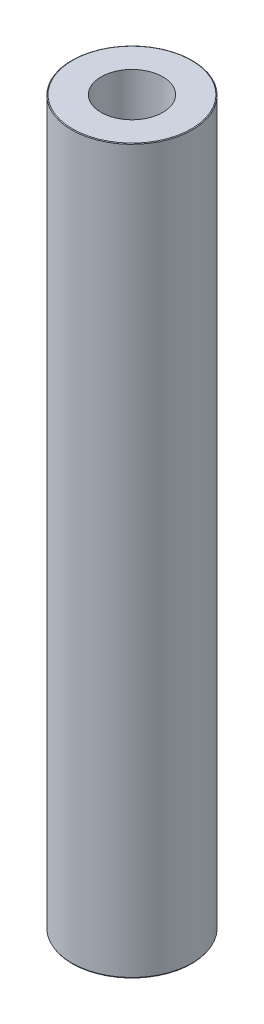
SolidWorks part; units mm, degrees
ref_plane "Front Plane" through (0, 0, 0) normal (0, 0, 1) x (1, 0, 0)
ref_plane "Top Plane" through (0, 0, 0) normal (0, 1, 0) x (1, 0, 0)
ref_plane "Right Plane" through (0, 0, 0) normal (1, 0, 0) x (0, 0, -1)
sketch "Sketch1" plane through (0, 0, 0) normal (0, 1, 0) x (1, 0, 0)
  circle A0 centre (0, 0) radius 50
  dimension "SHAFT_OD" = 100
extrude "Boss-Extrude1" add sketch "Sketch1" along normal blind 600
sketch "Sketch2" plane through (0, 0, 0) normal (0, 1, 0) x (1, 0, 0)
  circle A0 centre (0, 0) radius 25.6156
  dimension "BORE_D" = 51.2311
extrude "Cut-Extrude1" cut sketch "Sketch2" along normal through all
chamfer "Chamfer1" distance 0.3977 angle 60 2 edges at (0, 600, 50) (0, 0, 50) first distance on face at (0, 600, 50) first distance on face at (0, 0, 25.6156)
